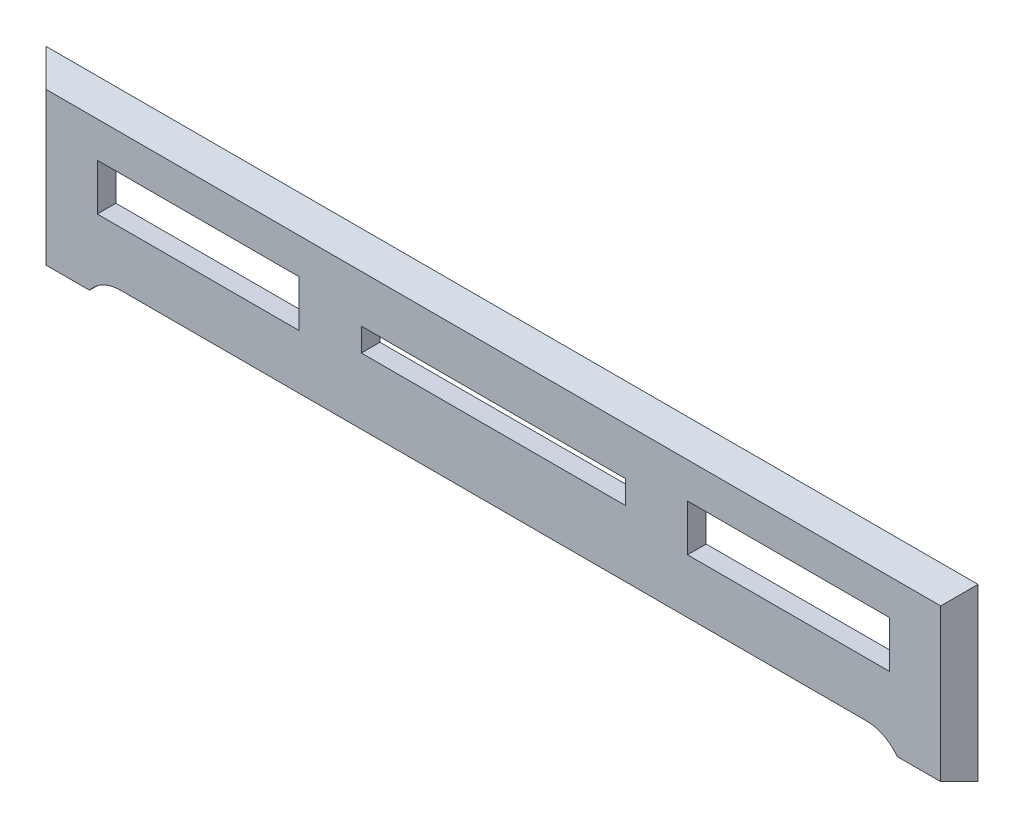
SolidWorks part; units mm, degrees
material "Teak"
ref_plane "Front Plane" through (0, 0, 0) normal (0, 0, 1) x (1, 0, 0)
ref_plane "Top Plane" through (0, 0, 0) normal (0, 1, 0) x (1, 0, 0)
ref_plane "Right Plane" through (0, 0, 0) normal (1, 0, 0) x (0, 0, -1)
sketch "Sketch1" plane through (0, 0, 0) normal (0, 0, 1) x (1, 0, 0)
  line L0 (0, 0) -> (0, -10)
  line L1 (60, 0) -> (540, 0)
  line L2 (0, 0) -> (0, 100)
  line L3 (0, 100) -> (600, 100)
  line L4 (600, 0) -> (600, 100)
  line L5 (0, -10) -> (40, -10)
  line L6 (600, 0) -> (600, -10)
  line L7 (600, -10) -> (560, -10)
  arc A0 (40, -10) -> (60, 0) centre (60, -25) cw
  arc A1 (560, -10) -> (540, 0) centre (540, -25) ccw
  dimension "D7" = 25
  dimension "D8" = 25
  dimension "D1" = 600
  dimension "D2" = 100
  dimension "D3" = 10
  dimension "D4" = 10
  dimension "D5" = 40
  dimension "D6" = 40
  dimension "D9" = 10
  dimension "D10" = 10
extrude "Boss-Extrude1" add sketch "Sketch1" along normal blind 12
sketch "Sketch2" plane through (0, 0, 12) normal (0, 0, 1) x (1, 0, 0)
  line L0 (600, 100) -> (0, 100) construction
  line L1 (45, 65) -> (175, 65)
  line L2 (45, 65) -> (45, 35)
  line L3 (45, 35) -> (175, 35)
  line L4 (175, 65) -> (175, 35)
  line L5 (215, 57.5) -> (385, 57.5)
  line L6 (215, 57.5) -> (215, 42.5)
  line L7 (215, 42.5) -> (385, 42.5)
  line L8 (385, 57.5) -> (385, 42.5)
  line L9 (425, 65) -> (555, 65)
  line L10 (425, 65) -> (425, 35)
  line L11 (425, 35) -> (555, 35)
  line L12 (555, 65) -> (555, 35)
  line L15 (600, 100) -> (0, 100) construction
  point P12 (300, 57.5)
  point P15 (300, 100)
  point P16 (175, 50)
  point P17 (215, 50)
  point P18 (425, 50)
  dimension "D1" = 130
  dimension "D3" = 130
  dimension "D4" = 30
  dimension "D5" = 15
  dimension "D6" = 170
  dimension "D7" = 40
  dimension "D8" = 40
  dimension "D9" = 35
extrude "Cut-Extrude1" cut sketch "Sketch2" against normal through all
chamfer "Chamfer1" distance 12 angle 45 3 edges at (600, 45, 12) (300, 100, 12) (0, 45, 12)
